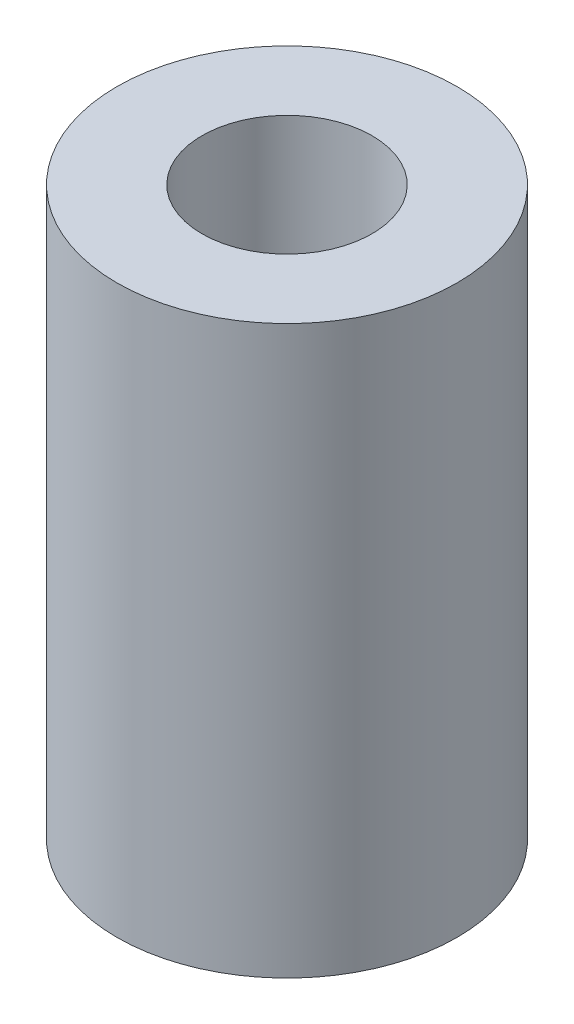
SolidWorks part; units mm, degrees
ref_plane "Front Plane" through (0, 0, 0) normal (0, 0, 1) x (1, 0, 0)
ref_plane "Top Plane" through (0, 0, 0) normal (0, 1, 0) x (1, 0, 0)
ref_plane "Right Plane" through (0, 0, 0) normal (1, 0, 0) x (0, 0, -1)
sketch "Sketch1" plane through (0, 0, 0) normal (0, 1, 0) x (1, 0, 0)
  circle A0 centre (0, 0) radius 1.5
  circle A1 centre (0, 0) radius 3
  dimension "D1" = 3
  dimension "D2" = 6
extrude "Boss-Extrude1" add sketch "Sketch1" along normal blind 10 contours A1 | A0
